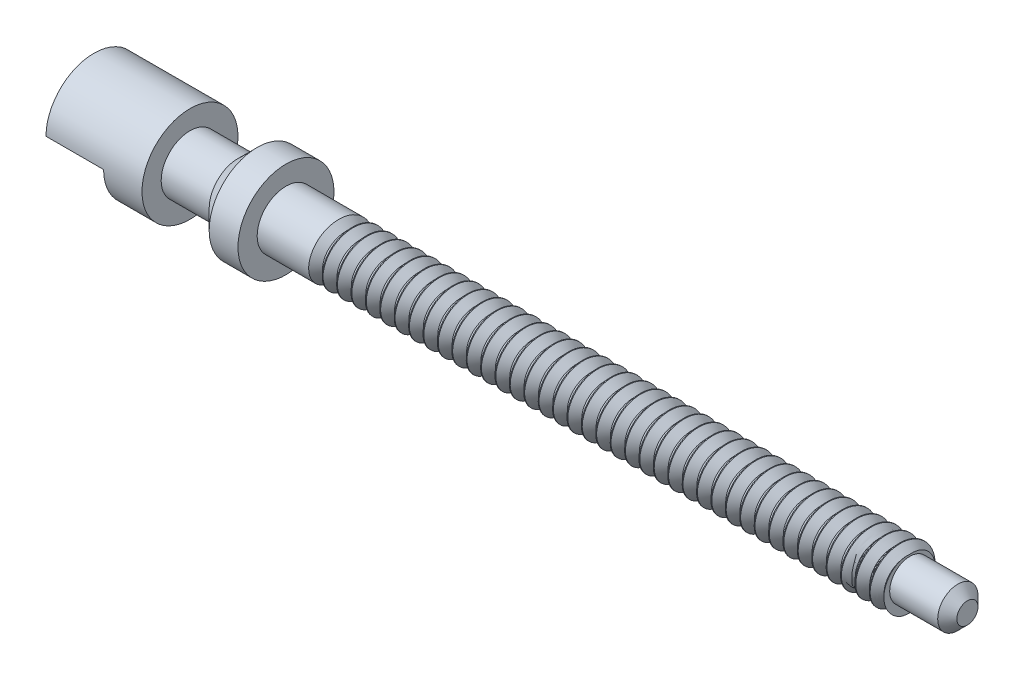
SolidWorks part; units mm, degrees
ref_plane "Front Plane" through (0, 0, 0) normal (0, 0, 1) x (1, 0, 0)
ref_plane "Top Plane" through (0, 0, 0) normal (0, 1, 0) x (1, 0, 0)
ref_plane "Right Plane" through (0, 0, 0) normal (1, 0, 0) x (0, 0, -1)
sketch "Sketch1" plane through (0, 0, 0) normal (0, 0, 1) x (1, 0, 0)
  line L0 (0, 0) -> (0, 0.5)
  line L1 (0, 0.5) -> (1, 0.5)
  line L2 (1, 0.5) -> (1, 0.3)
  line L3 (1, 0.3) -> (1.5, 0.3)
  line L4 (1.5, 0.3) -> (1.7, 0.5)
  line L5 (1.7, 0.5) -> (2, 0.5)
  line L6 (2, 0.5) -> (2, 0.3)
  line L7 (2, 0.3) -> (2.5, 0.3)
  line L8 (8.5, 0.3) -> (8.5, 0)
  line L9 (0, 0) -> (8.5, 0)
  line L10 (8.5, 0.3) -> (2.5, 0.3)
  dimension "D1" = 0.5
  dimension "D2" = 1
  dimension "D3" = 0.3
  dimension "D4" = 0.2
  dimension "D5" = 0.5
  dimension "D6" = 6.5
  dimension "D7" = 0.5
  dimension "D8" = 8.5
  dimension "D9" = 0.5
revolve "Revolve1" add sketch "Sketch1" angle 360 about L9
sketch "Sketch2" plane through (0, 0, 0) normal (0, 1, 0) x (1, 0, 0)
  line L0 (0, -0.5) -> (1, -0.5) construction
  line L1 (0, 0.5) -> (0.6, 0.5)
  line L2 (0, 0.5) -> (0, -0.5)
  line L3 (0, -0.5) -> (0.6, -0.5)
  line L4 (0.6, 0.5) -> (0.6, -0.5)
  dimension "D1" = 0.6
extrude "Cut-Extrude1" cut sketch "Sketch2" against normal through all
sketch "Sketch4" plane through (8.5, 0, 0) normal (1, 0, 0) x (0, 0, -1)
  circle A0 centre (0, 0) radius 0.3
curve "Helix/Spiral1" pitch 0.15 height 5.9625 radius 0.3 left hand yes centre (8.5, 0, 0) axis (-1, 0, 0) start towards (0, 1, 0)
sketch "Sketch5" plane through (0, 0, 0) normal (0, 0, 1) x (1, 0, 0)
  line L0 (8.425, 0.3) -> (8.5, 0.2293)
  line L1 (8.5, 0.3) -> (2.5, 0.3) construction
  line L2 (8.5, 0.3) -> (8.5, 0) construction
  line L3 (8.5, 0.2293) -> (8.5667, 0.3)
  line L4 (8.5667, 0.3) -> (8.425, 0.3)
sweep "Cut-Sweep1" cut profiles "Sketch5" path "Helix/Spiral1" align with end faces yes
sketch "Sketch7" plane through (0, 0, 0) normal (0, 0, 1) x (1, 0, 0)
  line L0 (8.6706, 0) -> (10.6931, 0) construction
  line L1 (8.5, 0) -> (9.1, 0)
  line L2 (9.1, 0) -> (9.1, 0.21)
  line L3 (9.1, 0.21) -> (8.5, 0.21)
  line L4 (8.5, 0.3) -> (8.5, 0) construction
  line L5 (8.5, 0.21) -> (8.5, 0)
  dimension "D1" = 0.21
  dimension "D2" = 0.6
revolve "Revolve2" add sketch "Sketch7" angle 360 about L0
chamfer "Chamfer1" distance 0.1 angle 45 1 edges at (9.1, 0, 0.21)
